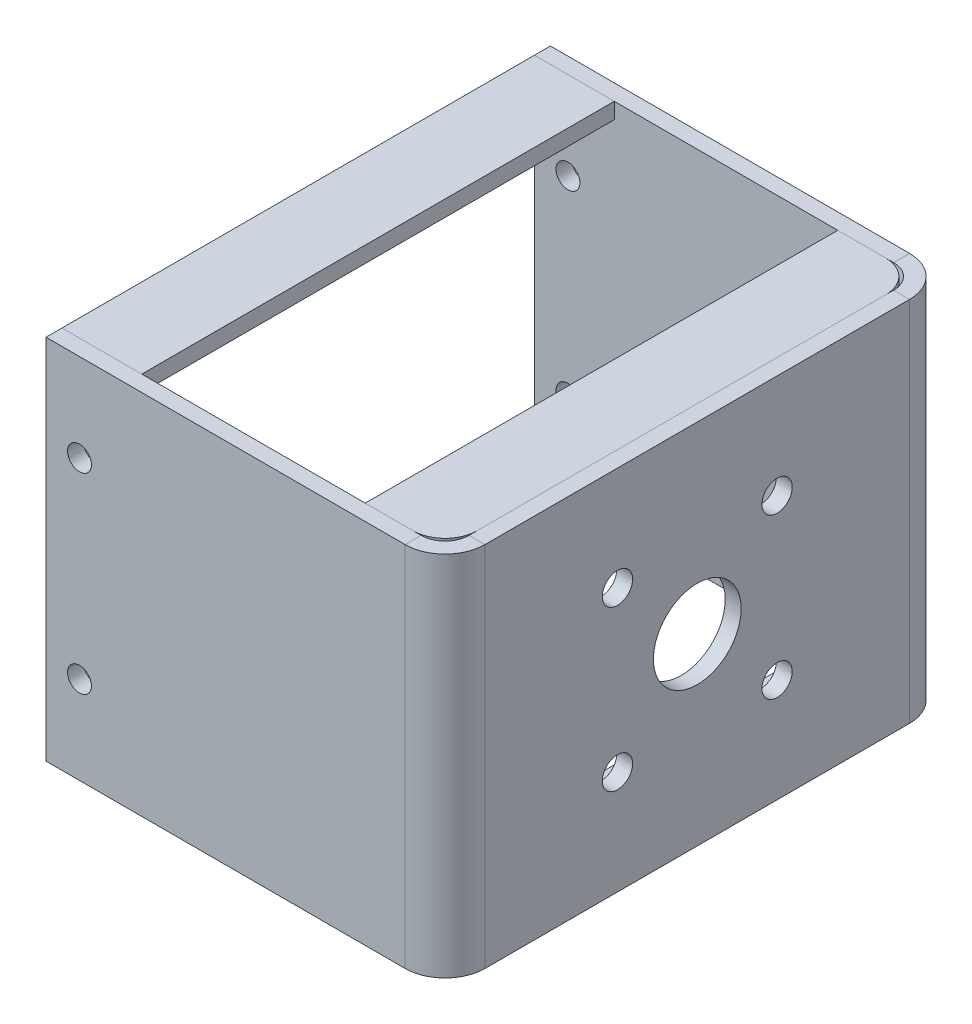
SolidWorks part; units mm, degrees
note: The reader was unsure of these and kept them because the rebuilt part matched: thickness of "Base-Flange1", "Edge-Flange1", "Sheet-Metal1", "Sheet-Metal2", "Sheet-Metal3", "Sheet-Metal4", "Sheet-Metal5", "Sheet-Metal6", "Sheet-Metal7", "Sheet-Metal11"; flange length of "Edge-Flange1".
material "Plain Carbon Steel"
ref_plane "Front Plane" through (0, 0, 0) normal (0, 0, 1) x (1, 0, 0)
ref_plane "Top Plane" through (0, 0, 0) normal (0, 1, 0) x (1, 0, 0)
ref_plane "Right Plane" through (0, 0, 0) normal (1, 0, 0) x (0, 0, -1)
sketch "Sketch1" plane through (0, 0, 0) normal (1, 0, 0) x (0, 0, -1)
  line L1 (-158, -115) -> (158, -115)
  line L2 (-158, -115) -> (-158, 115)
  line L3 (-158, 115) -> (158, 115)
  line L4 (158, -115) -> (158, 115)
  line L5 (-158, -115) -> (158, 115) construction
  line L6 (-158, 115) -> (158, -115) construction
  point P0 (0, 0)
  dimension "D1" = 316
  dimension "D2" = 230
base flange "Base-Flange1" sketch "Sketch1" thickness 10 reverse thickness direction no parameters "D1"=15
edge flange "Edge-Flange1" sketch "Sketch10" flange profiles "Sketch10", "Sketch11" flange angle 90 flange length 250 flange position material inside bend radius 15 thickness 10 relief rectangular parameters "D6"=10, "D8"=1
sketch "Sketch10" plane through (-10, 0, 158) normal (0, 0, 1) x (0, 1, 0)
  line L0 (115, 0) -> (-115, 0) construction
  line L1 (115, 0) -> (-115, 0)
  line L2 (-115, 0) -> (-115, 240)
  line L3 (-115, 240) -> (115, 240)
  line L4 (115, 240) -> (115, 0)
sketch "Sketch11" plane through (-10, 0, -158) normal (0, 0, -1) x (0, -1, 0)
  line L0 (115, 0) -> (-115, 0) construction
  line L1 (115, 0) -> (-115, 0)
  line L2 (-115, 0) -> (-115, 240)
  line L3 (-115, 240) -> (115, 240)
  line L4 (115, 240) -> (115, 0)
bend "EdgeBend1" bend radius 15 bend angle 90 parameters "D5"=1
bend "EdgeBend2" bend radius 15 bend angle 90 parameters "D5"=2
sketch "Sketch12" plane through (0, 0, 0) normal (1, 0, 0) x (0, 0, -1)
  line L0 (-158, -115) -> (158, 115) construction
  circle A0 centre (0, 0) radius 27.5
  dimension "D1" = 55
extrude "Cut-Extrude1" cut sketch "Sketch12" against normal blind 10
sketch "Sketch13" plane through (0, 0, 158) normal (0, 0, 1) x (1, 0, 0)
  line L1 (-250, 115) -> (-250, -115) construction
  circle A0 centre (-229, 60) radius 7.5
  dimension "D1" = 15
  dimension "D2" = 60
  dimension "D3" = 21
extrude "Cut-Extrude2" cut sketch "Sketch13" against normal through all
sketch "Sketch14" plane through (0, 0, 0) normal (1, 0, 0) x (0, 0, -1)
  line L1 (50, -50) -> (-50, -50) construction
  line L2 (50, -50) -> (50, 50) construction
  line L3 (50, 50) -> (-50, 50) construction
  line L4 (-50, -50) -> (-50, 50) construction
  line L5 (50, -50) -> (-50, 50) construction
  line L6 (50, 50) -> (-50, -50) construction
  circle A0 centre (-50, 50) radius 9.5
  circle A6 centre (0, 0) radius 70.7107 construction
  dimension "D1" = 19
  dimension "D2" = 100
extrude "Cut-Extrude3" cut sketch "Sketch14" against normal blind 10
mirror "Mirror1" about plane through (0, 0, 0) normal (0, 1, 0) of "Cut-Extrude2"
sketch "Sketch15" plane through (0, 115, 0) normal (0, 1, 0) x (1, 0, 0)
  line L0 (-250, 148) -> (-25, 148) construction
  line L1 (-60, 148) -> (-30, 148)
  line L2 (-60, 148) -> (-60, -148)
  line L3 (-60, -148) -> (-30, -148)
  line L4 (-10, 128) -> (-10, -128)
  line L5 (-25, -148) -> (-250, -148) construction
  line L6 (-10, 133) -> (-10, -133) construction
  line L8 (-250, 148) -> (-200, 148)
  line L9 (-250, 148) -> (-250, -148)
  line L10 (-250, -148) -> (-200, -148)
  line L11 (-200, 148) -> (-200, -148)
  arc A0 (-30, -148) -> (-10, -128) centre (-30, -128) ccw
  arc A1 (-30, 148) -> (-10, 128) centre (-30, 128) cw
  point P12 (-10, -148)
  dimension "D2" = 20
  dimension "D1" = 50
  dimension "D3" = 50
extrude "Boss-Extrude1" add sketch "Sketch15" against normal blind 10 separate body
mirror "Mirror2" about plane through (0, 0, 0) normal (0, 1, 0) of bodies 107 109
pattern_circular "CirPattern1" count 4 over 360 about axis through (0, 0, 0) along (1, 0, 0) of "Cut-Extrude3" reverse direction yes
sketch "Bend-Lines1" [suppressed] plane through (0, 0, 0) normal (0, 1, 0) x (1, 0, 0)
sketch "Bounding-Box1" [suppressed] plane through (0, 0, 0) normal (0, 1, 0) x (1, 0, 0)
sheet metal parameters "Sheet-Metal1" thickness 10 parameters "D1"=15
flat pattern "Flat-Pattern1" [suppressed]
sketch "Bend-Lines2" plane through (0, 0, 0) normal (0, 1, 0) x (1, 0, 0)
sketch3d "Bounding-Box2" [suppressed]
  line L0 (-162, -100, 0) -> (162, -100, 0) construction
  line L1 (-162, 100, 0) -> (162, 100, 0) construction
  line L2 (-162, -100, 0) -> (-162, 100, 0) construction
  line L3 (162, -100, 0) -> (162, 100, 0) construction
sheet metal parameters "Sheet-Metal2" thickness 10 parameters "D1"=15
flat pattern "Flat-Pattern1"
sketch "Bend-Lines2" plane through (0, 0, 0) normal (1, 0, 0) x (0, 0, -1)
  line L0 (152.708, -100) -> (152.708, 100) construction
  line L1 (-152.708, 100) -> (-152.708, -100) construction
  line L2 (152.708, -100) -> (152.708, 100) construction
  line L3 (-152.708, 100) -> (-152.708, -100) construction
sketch3d "Bounding-Box2" [suppressed]
  line L0 (416.4159, -100, 0) -> (-416.4159, -100, 0) construction
  line L1 (416.4159, 100, 0) -> (-416.4159, 100, 0) construction
  line L2 (416.4159, -100, 0) -> (416.4159, 100, 0) construction
  line L3 (-416.4159, -100, 0) -> (-416.4159, 100, 0) construction
bend of the flat pattern "Flatten-<EdgeBend1>1"
bend of the flat pattern "Flatten-<EdgeBend2>1"
sheet metal parameters "Sheet-Metal3" thickness 10 parameters "D1"=15
flat pattern "Flat-Pattern1"
sketch "Bend-Lines2" plane through (0, 0, 0) normal (1, 0, 0) x (0, 0, -1)
  line L0 (152.708, -100) -> (152.708, 100) construction
  line L1 (-152.708, 100) -> (-152.708, -100) construction
  line L2 (152.708, -100) -> (152.708, 100) construction
  line L3 (-152.708, 100) -> (-152.708, -100) construction
sketch3d "Bounding-Box2" [suppressed]
  line L0 (416.4159, -100, 0) -> (-416.4159, -100, 0) construction
  line L1 (416.4159, 100, 0) -> (-416.4159, 100, 0) construction
  line L2 (416.4159, -100, 0) -> (416.4159, 100, 0) construction
  line L3 (-416.4159, -100, 0) -> (-416.4159, 100, 0) construction
bend of the flat pattern "Flatten-<EdgeBend1>1"
bend of the flat pattern "Flatten-<EdgeBend2>1"
sheet metal parameters "Sheet-Metal4" thickness 10 parameters "D1"=15
flat pattern "Flat-Pattern1"
sketch "Bend-Lines2" plane through (0, 0, 0) normal (1, 0, 0) x (0, 0, -1)
  line L0 (152.708, -100) -> (152.708, 100) construction
  line L1 (-152.708, 100) -> (-152.708, -100) construction
  line L2 (152.708, -100) -> (152.708, 100) construction
  line L3 (-152.708, 100) -> (-152.708, -100) construction
sketch3d "Bounding-Box2" [suppressed]
  line L0 (416.4159, -100, 0) -> (-416.4159, -100, 0) construction
  line L1 (416.4159, 100, 0) -> (-416.4159, 100, 0) construction
  line L2 (416.4159, -100, 0) -> (416.4159, 100, 0) construction
  line L3 (-416.4159, -100, 0) -> (-416.4159, 100, 0) construction
bend of the flat pattern "Flatten-<EdgeBend1>1"
bend of the flat pattern "Flatten-<EdgeBend2>1"
sheet metal parameters "Sheet-Metal5" thickness 10 parameters "D1"=15
flat pattern "Flat-Pattern1"
sketch "Bend-Lines2" plane through (0, 0, 0) normal (1, 0, 0) x (0, 0, -1)
  line L0 (152.708, -100) -> (152.708, 100) construction
  line L1 (-152.708, 100) -> (-152.708, -100) construction
  line L2 (152.708, -100) -> (152.708, 100) construction
  line L3 (-152.708, 100) -> (-152.708, -100) construction
sketch3d "Bounding-Box2" [suppressed]
  line L0 (416.4159, -100, 0) -> (-416.4159, -100, 0) construction
  line L1 (416.4159, 100, 0) -> (-416.4159, 100, 0) construction
  line L2 (416.4159, -100, 0) -> (416.4159, 100, 0) construction
  line L3 (-416.4159, -100, 0) -> (-416.4159, 100, 0) construction
bend of the flat pattern "Flatten-<EdgeBend1>1"
bend of the flat pattern "Flatten-<EdgeBend2>1"
sheet metal parameters "Sheet-Metal6" thickness 10 parameters "D1"=15
flat pattern "Flat-Pattern1"
sketch "Bend-Lines2" plane through (0, 0, 0) normal (1, 0, 0) x (0, 0, -1)
  line L0 (148.708, -115) -> (148.708, 115) construction
  line L1 (-148.708, 115) -> (-148.708, -115) construction
  line L2 (148.708, -115) -> (148.708, 115) construction
  line L3 (-148.708, 115) -> (-148.708, -115) construction
sketch3d "Bounding-Box2" [suppressed]
  line L0 (389.4159, -115, 0) -> (-389.4159, -115, 0) construction
  line L1 (389.4159, 115, 0) -> (-389.4159, 115, 0) construction
  line L2 (389.4159, -115, 0) -> (389.4159, 115, 0) construction
  line L3 (-389.4159, -115, 0) -> (-389.4159, 115, 0) construction
bend of the flat pattern "Flatten-<EdgeBend1>1"
bend of the flat pattern "Flatten-<EdgeBend2>1"
sheet metal parameters "Sheet-Metal7" thickness 10 parameters "D1"=15
flat pattern "Flat-Pattern1"
sketch "Bend-Lines2" plane through (0, 0, 0) normal (1, 0, 0) x (0, 0, -1)
  line L0 (147.9226, -100) -> (147.9226, 100) construction
  line L1 (-147.9226, 100) -> (-147.9226, -100) construction
  line L2 (147.9226, -100) -> (147.9226, 100) construction
  line L3 (-147.9226, 100) -> (-147.9226, -100) construction
sketch3d "Bounding-Box2" [suppressed]
  line L0 (389.8451, -100, 0) -> (-389.8451, -100, 0) construction
  line L1 (389.8451, 100, 0) -> (-389.8451, 100, 0) construction
  line L2 (389.8451, -100, 0) -> (389.8451, 100, 0) construction
  line L3 (-389.8451, -100, 0) -> (-389.8451, 100, 0) construction
bend of the flat pattern "Flatten-<EdgeBend1>1"
bend of the flat pattern "Flatten-<EdgeBend2>1"
sheet metal parameters "Sheet-Metal11" thickness 10 parameters "D1"=15
flat pattern "Flat-Pattern1"
sketch "Bend-Lines2" plane through (0, 0, 0) normal (1, 0, 0) x (0, 0, -1)
  line L0 (148.708, -115) -> (148.708, 115) construction
  line L1 (-148.708, 115) -> (-148.708, -115) construction
  line L2 (148.708, -115) -> (148.708, 115) construction
  line L3 (-148.708, 115) -> (-148.708, -115) construction
sketch3d "Bounding-Box2" [suppressed]
  line L0 (389.4159, -115, 0) -> (-389.4159, -115, 0) construction
  line L1 (389.4159, 115, 0) -> (-389.4159, 115, 0) construction
  line L2 (389.4159, -115, 0) -> (389.4159, 115, 0) construction
  line L3 (-389.4159, -115, 0) -> (-389.4159, 115, 0) construction
bend of the flat pattern "Flatten-<EdgeBend1>1"
bend of the flat pattern "Flatten-<EdgeBend2>1"
